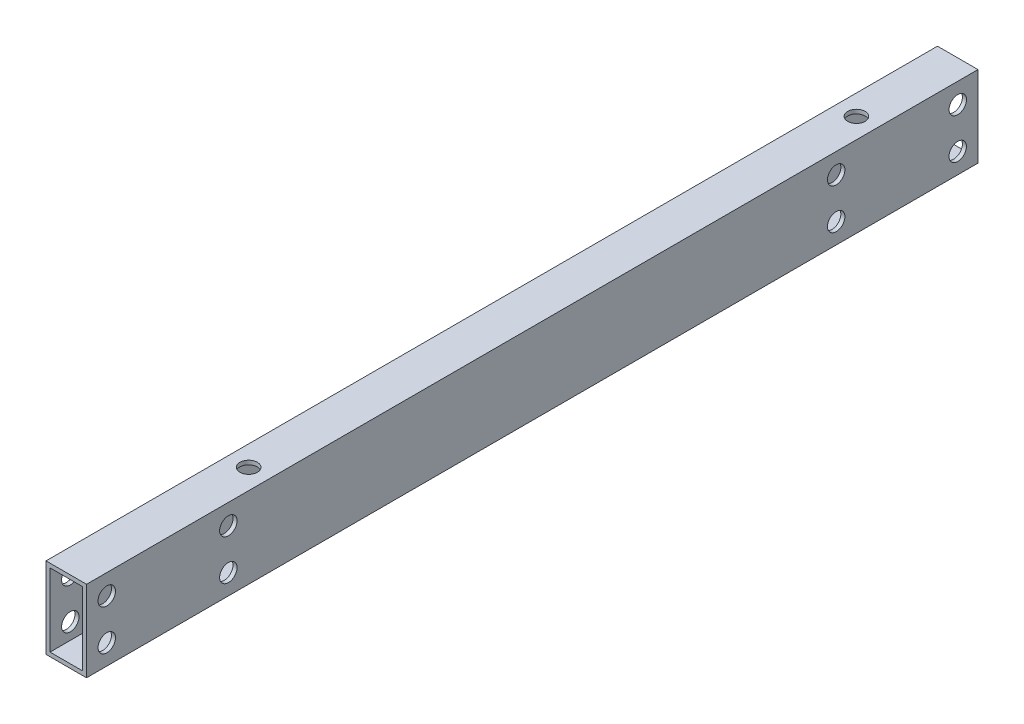
SolidWorks part; units mm, degrees
material "5052-H34"
ref_plane "正面" through (0, 0, 0) normal (0, 0, 1) x (1, 0, 0)
ref_plane "平面" through (0, 0, 0) normal (0, 1, 0) x (1, 0, 0)
ref_plane "右側面" through (0, 0, 0) normal (1, 0, 0) x (0, 0, -1)
sketch "ｽｹｯﾁ1" plane through (0, 0, 0) normal (0, 0, 1) x (1, 0, 0)
  line L1 (-5, 10) -> (5, 10)
  line L2 (-5, 10) -> (-5, -10)
  line L3 (-5, -10) -> (5, -10)
  line L4 (5, 10) -> (5, -10)
  line L5 (-5, 10) -> (5, -10) construction
  line L6 (-5, -10) -> (5, 10) construction
  point P0 (0, 0)
  dimension "D1" = 10
  dimension "D2" = 20
extrude "押し出し-薄板1" add sketch "ｽｹｯﾁ1" along normal blind 220 thin thin type one direction reverse wall 1
sketch "ｽｹｯﾁ2" plane through (5, 0, 0) normal (1, 0, 0) x (0, 0, -1)
  line L0 (0, 0) -> (-20, 0) construction
  line L1 (0, -10) -> (0, 10) construction
  line L2 (-20, 5) -> (-20, 0) construction
  line L3 (-5, 5) -> (-35, 5) construction
  line L4 (-5, 5) -> (-5, -5) construction
  line L5 (-5, -5) -> (-35, -5) construction
  line L6 (-35, 5) -> (-35, -5) construction
  line L7 (-5, 5) -> (-35, -5) construction
  line L8 (-5, -5) -> (-35, 5) construction
  line L9 (-110, 10) -> (-110, -10) construction
  line L10 (-220, 10) -> (0, 10) construction
  line L11 (-220, -10) -> (0, -10) construction
  line L12 (-215, -5) -> (-185, 5) construction
  line L13 (-215, 5) -> (-185, -5) construction
  line L14 (-185, 5) -> (-185, -5) construction
  line L15 (-215, -5) -> (-185, -5) construction
  line L16 (-215, 5) -> (-215, -5) construction
  line L17 (-215, 5) -> (-185, 5) construction
  line L18 (-200, 5) -> (-200, 0) construction
  line L19 (-220, 0) -> (-200, 0) construction
  circle A0 centre (-5, 5) radius 2.15
  circle A1 centre (-5, -5) radius 2.15
  circle A2 centre (-35, 5) radius 2.15
  circle A3 centre (-35, -5) radius 2.15
  circle A4 centre (-185, -5) radius 2.15
  circle A5 centre (-185, 5) radius 2.15
  circle A6 centre (-215, -5) radius 2.15
  circle A7 centre (-215, 5) radius 2.15
  dimension "D4" = 4.3
  dimension "D1" = 30
  dimension "D2" = 10
  dimension "D3" = 5
extrude "ｶｯﾄ - 押し出し1" cut sketch "ｽｹｯﾁ2" against normal through all
sketch "ｽｹｯﾁ3" plane through (0, 10, 0) normal (0, 1, 0) x (1, 0, 0)
  line L0 (-5, -100) -> (5, -100) construction
  line L1 (-5, -220) -> (-5, 0) construction
  line L2 (5, -220) -> (5, 0) construction
  line L3 (0, -100) -> (0, -25) construction
  circle A0 centre (0, -25) radius 2.15
  circle A1 centre (0, -175) radius 2.15
  dimension "D2" = 4.3
  dimension "D1" = 100
  dimension "D3" = 150
extrude "ｶｯﾄ - 押し出し2" cut sketch "ｽｹｯﾁ3" against normal through all
